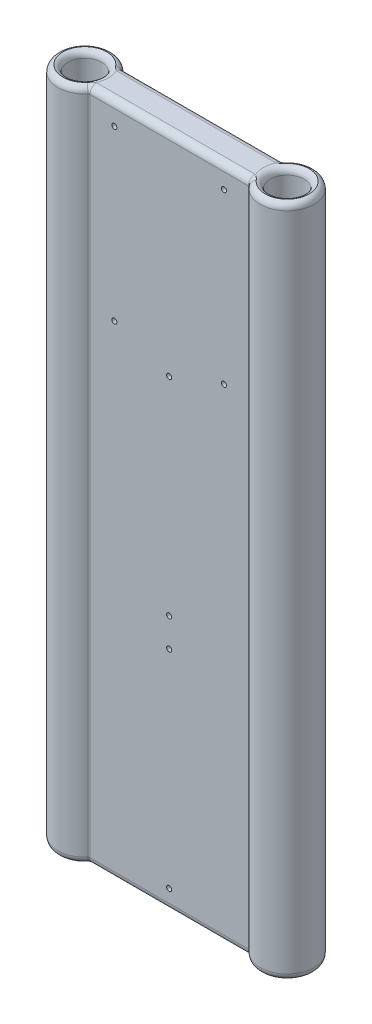
SolidWorks part; units mm, degrees
material "Custom Plastic"
ref_plane "Front Plane" through (0, 0, 0) normal (0, 0, 1) x (1, 0, 0)
ref_plane "Top Plane" through (0, 0, 0) normal (0, 1, 0) x (1, 0, 0)
ref_plane "Right Plane" through (0, 0, 0) normal (1, 0, 0) x (0, 0, -1)
sketch "Sketch1" plane through (0, 0, 0) normal (0, 1, 0) x (1, 0, 0)
  line L0 (-42.5677, 0) -> (42.5677, 0) construction
  line L3 (0, 39.8475) -> (0, -21.5223) construction
  line L8 (29.845, -6.35) -> (-29.845, -6.35)
  line L9 (-29.845, 6.35) -> (29.845, 6.35)
  circle A2 centre (38.1, 0) radius 6.35
  circle A3 centre (-38.1, 0) radius 6.35
  arc A4 (-48.26, 0) -> (-30.3685, 6.5916) centre (-38.1, 0) cw
  arc A5 (30.3685, -6.5916) -> (48.26, 0) centre (38.1, 0) ccw
  circle A6 centre (-38.1, 0) radius 10.16 construction
  arc A7 (-30.3685, -6.5916) -> (-48.26, 0) centre (-38.1, 0) cw
  circle A8 centre (38.1, 0) radius 10.16 construction
  arc A9 (48.26, 0) -> (30.3685, 6.5916) centre (38.1, 0) ccw
  arc A12 (29.845, 6.35) -> (30.3685, 6.5916) centre (29.845, 7.0379) ccw
  arc A13 (29.845, -6.35) -> (30.3685, -6.5916) centre (29.845, -7.0379) cw
  arc A14 (-29.845, -6.35) -> (-30.3685, -6.5916) centre (-29.845, -7.0379) ccw
  arc A15 (-29.845, 6.35) -> (-30.3685, 6.5916) centre (-29.845, 7.0379) cw
  point P3 (0, 0)
  point P32 (46.0311, 6.35)
  point P39 (-30.1689, -6.35)
  point P46 (-46.0311, -6.35)
  dimension "D1" = 96.52
  dimension "D2" = 12.7
  dimension "D7" = 59.69
  dimension "D3" = 38.1
  dimension "D4" = 3.81
  dimension "D6" = 12.7
  dimension "D5" = 3.81
extrude "Boss-Extrude1" add sketch "Sketch1" along normal mid plane 254
fillet "Fillet1" radius 2.54 20 edges at (38.1, -127, 6.35) (-38.1, -127, -6.35) (-48.26, -127, 0) (-30.1333, -127, 6.4133) (0, -127, 6.35) (30.1333, -127, 6.4133) (48.26, -127, 0) (30.1333, -127, -6.4133) (0, -127, -6.35) (-30.1333, -127, -6.4133) (38.1, 127, 6.35) (-48.26, 127, 0) (-30.1333, 127, -6.4133) (0, 127, -6.35) (30.1333, 127, -6.4133) (48.26, 127, 0) (30.1333, 127, 6.4133) (0, 127, 6.35) (-30.1333, 127, 6.4133) (-38.1, 127, -6.35)
sketch "Sketch2" plane through (0, 0, -6.35) normal (0, 0, -1) x (-1, 0, 0)
  line L0 (27.051, 3.9456) -> (-27.051, 3.9456) construction
  line L1 (27.051, 3.9456) -> (27.051, 97.9256) construction
  line L2 (27.051, 97.9256) -> (-27.051, 97.9256) construction
  line L3 (-27.051, 3.9456) -> (-27.051, 97.9256) construction
  line L4 (27.051, 3.9456) -> (-27.051, 97.9256) construction
  line L5 (27.051, 97.9256) -> (-27.051, 3.9456) construction
  line L12 (-2.8708, -15.2743) -> (-2.8708, -11.4643) construction
  line L13 (0.9392, -15.2743) -> (0.9392, -11.4643) construction
  line L14 (-2.8708, -11.4643) -> (0.9392, -11.4643) construction
  line L15 (-37.9665, -54.3182) -> (37.9665, -54.3182) construction
  line L16 (-2.8708, -97.1722) -> (0.9392, -97.1722) construction
  line L17 (0.9392, -93.3622) -> (0.9392, -97.1722) construction
  line L18 (-2.8708, -93.3622) -> (-2.8708, -97.1722) construction
  circle A0 centre (-27.051, 97.9256) radius 0.9525
  circle A1 centre (27.051, 97.9256) radius 0.9525
  circle A2 centre (27.051, 3.9456) radius 0.9525
  circle A3 centre (-27.051, 3.9456) radius 0.9525
  arc A7 (-2.8708, -93.3622) -> (0.9392, -93.3622) centre (-0.9658, -93.3622) cw construction
  arc A8 (-2.8708, -15.2743) -> (0.9392, -15.2743) centre (-0.9658, -15.2743) ccw construction
  circle A9 centre (-0.9658, -15.2743) radius 0.9525
  circle A10 centre (-0.9658, -93.3622) radius 0.9525
  point P0 (0, 50.9356)
  dimension "D3" = 1.905
  dimension "D4" = 39.044
  dimension "D1" = 93.98
  dimension "D2" = 54.102
  dimension "D5" = 3.81
  dimension "D6" = 39.044
extrude "Cut-Extrude1" cut sketch "Sketch2" against normal blind 3.81 and the other way blind 3.81 contours A9 | A10 | A3 | A2 | A0 | A1
sketch "Sketch3" plane through (0, 0, 6.35) normal (0, 0, 1) x (1, 0, 0)
  line L0 (-1.905, -41.5283) -> (-3.3352, -37.7183) construction
  line L1 (1.905, -41.5283) -> (1.905, -37.7183) construction
  line L2 (-3.3352, -37.7183) -> (1.905, -37.7183) construction
  line L3 (-37.0006, -80.5723) -> (37.0006, -80.5723) construction
  line L4 (-3.3352, -123.4262) -> (1.905, -123.4262) construction
  line L5 (1.905, -119.6162) -> (1.905, -123.4262) construction
  line L6 (-1.905, -119.6162) -> (-3.3352, -123.4262) construction
  line L7 (-1.905, 47.3984) -> (-3.2749, 51.2084) construction
  line L8 (1.905, 47.3984) -> (1.905, 51.2084) construction
  line L9 (-3.2749, 51.2084) -> (1.905, 51.2084) construction
  line L10 (-37.0006, 8.3545) -> (37.0006, 8.3545) construction
  line L11 (-3.2749, -34.4995) -> (1.905, -34.4995) construction
  line L12 (1.905, -30.6895) -> (1.905, -34.4995) construction
  line L13 (-1.905, -30.6895) -> (-3.2749, -34.4995) construction
  line L14 (-20.6375, 55.1759) -> (20.6375, 55.1759) construction
  line L15 (-20.6375, 55.1759) -> (-20.6375, 118.6759) construction
  line L16 (-20.6375, 118.6759) -> (20.6375, 118.6759) construction
  line L17 (20.6375, 55.1759) -> (20.6375, 118.6759) construction
  line L18 (-20.6375, 55.1759) -> (20.6375, 118.6759) construction
  line L19 (-20.6375, 118.6759) -> (20.6375, 55.1759) construction
  arc A0 (-1.905, -119.6162) -> (1.905, -119.6162) centre (0, -119.6162) cw construction
  arc A1 (-1.905, -41.5283) -> (1.905, -41.5283) centre (0, -41.5283) ccw construction
  circle A2 centre (0, -41.5283) radius 0.9525
  circle A3 centre (0, -119.6162) radius 0.9525
  arc A4 (-1.905, -30.6895) -> (1.905, -30.6895) centre (0, -30.6895) cw construction
  arc A5 (-1.905, 47.3984) -> (1.905, 47.3984) centre (0, 47.3984) ccw construction
  circle A6 centre (0, 47.3984) radius 0.9525
  circle A7 centre (0, -30.6895) radius 0.9525
  circle A8 centre (-20.6375, 118.6759) radius 0.9525
  circle A9 centre (20.6375, 118.6759) radius 0.9525
  circle A10 centre (20.6375, 55.1759) radius 0.9525
  circle A11 centre (-20.6375, 55.1759) radius 0.9525
  point P0 (0, -80.5723)
  point P21 (0, 8.3545)
  point P36 (0, 86.9259)
  dimension "D9" = 1.905
  dimension "D1" = 3.81
  dimension "D2" = 39.044
  dimension "D3" = 39.044
  dimension "D4" = 3.81
  dimension "D5" = 39.044
  dimension "D6" = 39.044
  dimension "D7" = 63.5
  dimension "D8" = 41.275
extrude "Cut-Extrude2" cut sketch "Sketch3" against normal blind 3.81
